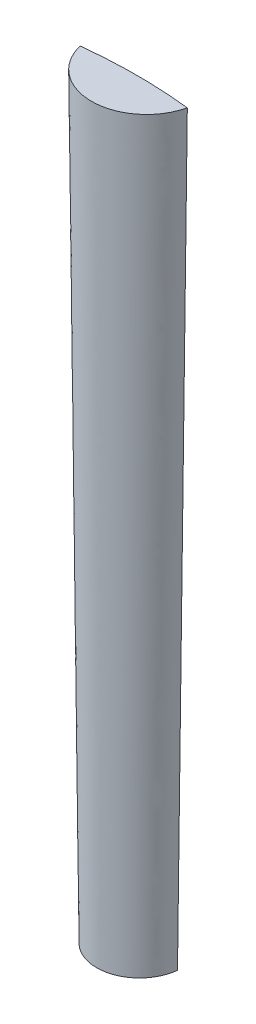
SolidWorks part; units mm, degrees
material "Maple"
ref_plane "Front Plane" through (0, 0, 0) normal (0, 0, 1) x (1, 0, 0)
ref_plane "Top Plane" through (0, 0, 0) normal (0, 1, 0) x (1, 0, 0)
ref_plane "Right Plane" through (0, 0, 0) normal (1, 0, 0) x (0, 0, -1)
sketch "Model" plane through (0, 0, 0) normal (0, 0, 1) x (1, 0, 0)
  line L0 (47.9999, 0) -> (57.149, 660.4)
  line L1 (40.86, 0) -> (46.3494, 660.4)
  line L2 (33.72, 0) -> (35.5498, 660.4)
  line L3 (26.5801, 0) -> (24.7503, 660.4)
  line L4 (19.4401, 0) -> (13.9507, 660.4)
  line L5 (12.3002, 0) -> (3.1511, 660.4)
  line L6 (51.151, 0) -> (60.3001, 660.4)
  line L7 (9.1491, 0) -> (0, 660.4)
  line L8 (51.659, 0) -> (43.9219, 0)
  line L9 (52.1725, 37.0654) -> (44.3327, 37.0654)
  line L10 (52.6572, 72.0505) -> (44.7205, 72.0505)
  line L11 (53.1147, 105.072) -> (45.0865, 105.072)
  line L12 (53.5465, 136.2402) -> (45.4319, 136.2402)
  line L13 (53.954, 165.659) -> (45.7579, 165.659)
  line L14 (54.3387, 193.4267) -> (46.0657, 193.4267)
  line L15 (54.7018, 219.6359) -> (46.3562, 219.6359)
  line L16 (55.0445, 244.3741) -> (46.6304, 244.3741)
  line L17 (55.368, 267.7238) -> (46.8891, 267.7238)
  line L18 (55.6734, 289.763) -> (47.1334, 289.763)
  line L19 (55.9616, 310.5653) -> (47.364, 310.5653)
  line L20 (56.2336, 330.2) -> (47.5816, 330.2)
  line L21 (56.4903, 348.7327) -> (47.787, 348.7327)
  line L22 (56.7327, 366.2252) -> (47.9808, 366.2252)
  line L23 (56.9614, 382.736) -> (48.1638, 382.736)
  line L24 (57.1773, 398.3201) -> (48.3365, 398.3201)
  line L25 (57.3811, 413.0295) -> (48.4996, 413.0295)
  line L26 (57.5734, 426.9133) -> (48.6534, 426.9133)
  line L27 (57.755, 440.0179) -> (48.7987, 440.0179)
  line L28 (57.9263, 452.387) -> (48.9358, 452.387)
  line L29 (58.0881, 464.0619) -> (49.0652, 464.0619)
  line L30 (58.2407, 475.0815) -> (49.1873, 475.0815)
  line L31 (58.3848, 485.4826) -> (49.3026, 485.4826)
  line L32 (58.5208, 495.3) -> (49.4114, 495.3)
  line L33 (44.9379, 0) -> (36.782, 0)
  line L34 (45.3487, 37.0654) -> (36.9874, 37.0654)
  line L35 (45.7365, 72.0505) -> (37.1813, 72.0505)
  line L36 (46.1025, 105.072) -> (37.3643, 105.072)
  line L37 (46.4479, 136.2402) -> (37.537, 136.2402)
  line L38 (46.7739, 165.659) -> (37.7, 165.659)
  line L39 (47.0817, 193.4267) -> (37.8539, 193.4267)
  line L40 (47.3722, 219.6359) -> (37.9991, 219.6359)
  line L41 (47.6464, 244.3741) -> (38.1362, 244.3741)
  line L42 (47.9051, 267.7238) -> (38.2656, 267.7238)
  line L43 (48.1494, 289.763) -> (38.3877, 289.763)
  line L44 (48.38, 310.5653) -> (38.503, 310.5653)
  line L45 (48.5976, 330.2) -> (38.6118, 330.2)
  line L46 (48.803, 348.7327) -> (38.7145, 348.7327)
  line L47 (48.9968, 366.2252) -> (38.8114, 366.2252)
  line L48 (49.1798, 382.736) -> (38.9029, 382.736)
  line L49 (49.3525, 398.3201) -> (38.9893, 398.3201)
  line L50 (49.5156, 413.0295) -> (39.0708, 413.0295)
  line L51 (49.6694, 426.9133) -> (39.1478, 426.9133)
  line L52 (49.8147, 440.0179) -> (39.2204, 440.0179)
  line L53 (49.9518, 452.387) -> (39.2889, 452.387)
  line L54 (50.0812, 464.0619) -> (39.3536, 464.0619)
  line L55 (50.2033, 475.0815) -> (39.4147, 475.0815)
  line L56 (50.3186, 485.4826) -> (39.4723, 485.4826)
  line L57 (50.4274, 495.3) -> (39.5267, 495.3)
  line L58 (37.798, 0) -> (29.6421, 0)
  line L59 (38.0034, 37.0654) -> (29.6421, 37.0654)
  line L60 (38.1973, 72.0505) -> (29.6421, 72.0505)
  line L61 (38.3803, 105.072) -> (29.6421, 105.072)
  line L62 (38.553, 136.2402) -> (29.6421, 136.2402)
  line L63 (38.716, 165.659) -> (29.6421, 165.659)
  line L64 (38.8699, 193.4267) -> (29.6421, 193.4267)
  line L65 (39.0151, 219.6359) -> (29.6421, 219.6359)
  line L66 (39.1522, 244.3741) -> (29.6421, 244.3741)
  line L67 (39.2816, 267.7238) -> (29.6421, 267.7238)
  line L68 (39.4037, 289.763) -> (29.6421, 289.763)
  line L69 (39.519, 310.5653) -> (29.6421, 310.5653)
  line L70 (39.6278, 330.2) -> (29.6421, 330.2)
  line L71 (39.7305, 348.7327) -> (29.6421, 348.7327)
  line L72 (39.8274, 366.2252) -> (29.6421, 366.2252)
  line L73 (39.9189, 382.736) -> (29.6421, 382.736)
  line L74 (40.0053, 398.3201) -> (29.6421, 398.3201)
  line L75 (40.0868, 413.0295) -> (29.6421, 413.0295)
  line L76 (40.1638, 426.9133) -> (29.6421, 426.9133)
  line L77 (40.2364, 440.0179) -> (29.6421, 440.0179)
  line L78 (40.3049, 452.387) -> (29.6421, 452.387)
  line L79 (40.3696, 464.0619) -> (29.6421, 464.0619)
  line L80 (40.4307, 475.0815) -> (29.6421, 475.0815)
  line L81 (40.4883, 485.4826) -> (29.6421, 485.4826)
  line L82 (40.5427, 495.3) -> (29.6421, 495.3)
  line L83 (30.6581, 0) -> (22.5021, 0)
  line L84 (30.6581, 37.0654) -> (22.2967, 37.0654)
  line L85 (30.6581, 72.0505) -> (22.1028, 72.0505)
  line L86 (30.6581, 105.072) -> (21.9199, 105.072)
  line L87 (30.6581, 136.2402) -> (21.7471, 136.2402)
  line L88 (30.6581, 165.659) -> (21.5841, 165.659)
  line L89 (30.6581, 193.4267) -> (21.4302, 193.4267)
  line L90 (30.6581, 219.6359) -> (21.285, 219.6359)
  line L91 (30.6581, 244.3741) -> (21.1479, 244.3741)
  line L92 (30.6581, 267.7238) -> (21.0185, 267.7238)
  line L93 (30.6581, 289.763) -> (20.8964, 289.763)
  line L94 (30.6581, 310.5653) -> (20.7811, 310.5653)
  line L95 (30.6581, 330.2) -> (20.6723, 330.2)
  line L96 (30.6581, 348.7327) -> (20.5696, 348.7327)
  line L97 (30.6581, 366.2252) -> (20.4727, 366.2252)
  line L98 (30.6581, 382.736) -> (20.3812, 382.736)
  line L99 (30.6581, 398.3201) -> (20.2948, 398.3201)
  line L100 (30.6581, 413.0295) -> (20.2133, 413.0295)
  line L101 (30.6581, 426.9133) -> (20.1364, 426.9133)
  line L102 (30.6581, 440.0179) -> (20.0637, 440.0179)
  line L103 (30.6581, 452.387) -> (19.9952, 452.387)
  line L104 (30.6581, 464.0619) -> (19.9305, 464.0619)
  line L105 (30.6581, 475.0815) -> (19.8694, 475.0815)
  line L106 (30.6581, 485.4826) -> (19.8118, 485.4826)
  line L107 (30.6581, 495.3) -> (19.7574, 495.3)
  line L108 (23.5181, 0) -> (15.3622, 0)
  line L109 (23.3127, 37.0654) -> (14.9514, 37.0654)
  line L110 (23.1188, 72.0505) -> (14.5636, 72.0505)
  line L111 (22.9359, 105.072) -> (14.1977, 105.072)
  line L112 (22.7631, 136.2402) -> (13.8522, 136.2402)
  line L113 (22.6001, 165.659) -> (13.5262, 165.659)
  line L114 (22.4462, 193.4267) -> (13.2184, 193.4267)
  line L115 (22.301, 219.6359) -> (12.9279, 219.6359)
  line L116 (22.1639, 244.3741) -> (12.6538, 244.3741)
  line L117 (22.0345, 267.7238) -> (12.395, 267.7238)
  line L118 (21.9124, 289.763) -> (12.1507, 289.763)
  line L119 (21.7971, 310.5653) -> (11.9202, 310.5653)
  line L120 (21.6883, 330.2) -> (11.7025, 330.2)
  line L121 (21.5856, 348.7327) -> (11.4971, 348.7327)
  line L122 (21.4887, 366.2252) -> (11.3033, 366.2252)
  line L123 (21.3972, 382.736) -> (11.1203, 382.736)
  line L124 (21.3108, 398.3201) -> (10.9476, 398.3201)
  line L125 (21.2293, 413.0295) -> (10.7845, 413.0295)
  line L126 (21.1524, 426.9133) -> (10.6307, 426.9133)
  line L127 (21.0797, 440.0179) -> (10.4854, 440.0179)
  line L128 (21.0112, 452.387) -> (10.3483, 452.387)
  line L129 (20.9465, 464.0619) -> (10.2189, 464.0619)
  line L130 (20.8854, 475.0815) -> (10.0968, 475.0815)
  line L131 (20.8278, 485.4826) -> (9.9815, 485.4826)
  line L132 (20.7734, 495.3) -> (9.8727, 495.3)
  line L133 (16.3782, 0) -> (8.6411, 0)
  line L134 (15.9674, 37.0654) -> (8.1276, 37.0654)
  line L135 (15.5796, 72.0505) -> (7.6429, 72.0505)
  line L136 (15.2137, 105.072) -> (7.1854, 105.072)
  line L137 (14.8682, 136.2402) -> (6.7536, 136.2402)
  line L138 (14.5422, 165.659) -> (6.3461, 165.659)
  line L139 (14.2344, 193.4267) -> (5.9614, 193.4267)
  line L140 (13.9439, 219.6359) -> (5.5983, 219.6359)
  line L141 (13.6698, 244.3741) -> (5.2556, 244.3741)
  line L142 (13.411, 267.7238) -> (4.9321, 267.7238)
  line L143 (13.1667, 289.763) -> (4.6267, 289.763)
  line L144 (12.9362, 310.5653) -> (4.3386, 310.5653)
  line L145 (12.7185, 330.2) -> (4.0665, 330.2)
  line L146 (12.5131, 348.7327) -> (3.8098, 348.7327)
  line L147 (12.3193, 366.2252) -> (3.5675, 366.2252)
  line L148 (12.1363, 382.736) -> (3.3387, 382.736)
  line L149 (11.9636, 398.3201) -> (3.1228, 398.3201)
  line L150 (11.8005, 413.0295) -> (2.919, 413.0295)
  line L151 (11.6467, 426.9133) -> (2.7267, 426.9133)
  line L152 (11.5014, 440.0179) -> (2.5451, 440.0179)
  line L153 (11.3643, 452.387) -> (2.3738, 452.387)
  line L154 (11.2349, 464.0619) -> (2.212, 464.0619)
  line L155 (11.1128, 475.0815) -> (2.0594, 475.0815)
  line L156 (10.9975, 485.4826) -> (1.9153, 485.4826)
  line L157 (10.8887, 495.3) -> (1.7793, 495.3)
  point P316 (0, 0)
ref_plane "Plane1" through (0, 37.07, 0) normal (0, 1, 0) x (1, 0, 0)
ref_plane "Plane2" through (0, 413.03, 0) normal (0, 1, 0) x (1, 0, 0)
sketch "Sketch2" plane through (0, 37.07, 0) normal (0, 1, 0) x (1, 0, 0)
  line L0 (22.5021, 0) -> (37.798, 0) construction
  line L4 (30.6581, 0) -> (22.5021, 0) construction
  line L5 (30.6581, 0) -> (22.2967, 0) construction
  line L6 (37.798, 0) -> (29.6421, 0) construction
  line L7 (30.1501, 0) -> (30.1501, -241.3) construction
  line L8 (30.1501, 0) -> (30.1501, -20) construction
  line L9 (30.1501, 0) -> (30.1501, 60) construction
  line L10 (8.7751, 0) -> (51.5251, 0) construction
  arc A0 (51.4416, -0.9412) -> (8.8585, -0.9412) centre (30.1501, -241.3) ccw
  arc A1 (8.7751, 0) -> (8.8585, -0.9412) centre (30.1501, 1.4219) ccw construction
  arc A3 (8.8585, -0.9412) -> (51.4416, -0.9412) centre (30.1501, 1.4219) ccw
  point P17 (30.1501, 0)
  point P20 (51.4076, -0.9253)
  dimension "D1" = 241.3
  dimension "D2" = 20
  dimension "D3" = 60
  dimension "D4" = 42.75
sketch "Sketch4" plane through (0, 413.03, 0) normal (0, 1, 0) x (1, 0, 0)
  line L0 (37.798, 0) -> (22.5021, 0) construction
  line L1 (37.798, 0) -> (29.6421, 0) construction
  line L2 (44.9379, 0) -> (36.782, 0) construction
  line L3 (30.6581, 0) -> (22.5021, 0) construction
  line L4 (30.6581, 0) -> (22.2967, 0) construction
  line L5 (30.1501, 0) -> (30.1501, -241.3) construction
  line L6 (30.1501, 0) -> (30.1501, -22.6) construction
  line L7 (57.2001, 0) -> (3.1001, 0) construction
  circle A0 centre (30.1501, -241.3) radius 241.3 construction
  arc A1 (57.2001, 0) -> (56.8889, -1.4861) centre (30.1501, 4.8875) cw construction
  arc A2 (3.4112, -1.4861) -> (56.8889, -1.4861) centre (30.1501, -241.3) cw
  arc A3 (3.4112, -1.4861) -> (3.1001, 0) centre (30.1501, 4.8875) cw construction
  arc A4 (56.8889, -1.4861) -> (3.4112, -1.4861) centre (30.1501, 4.8875) cw
  point P18 (30.1501, 0)
  point P21 (53.3782, 3.2801)
  point P22 (1.6999, -2.0699)
  dimension "D1" = 241.3
  dimension "D2" = 22.6
  dimension "D3" = 54.1
loft "Loft1" add profiles "Sketch4", "Sketch2" connector at (3.4112, 413.03, 1.4861) connector at (8.8585, 37.07, 0.9412)
sketch "Sketch5" plane through (0, 0, 0) normal (0, 0, 1) x (1, 0, 0)
  line L0 (51.151, 0) -> (51.151, -3.25) construction
  line L1 (51.151, -3.25) -> (9.1491, -3.25) construction
  line L2 (9.1491, -3.25) -> (9.1491, 0) construction
  line L3 (51.151, 0) -> (9.1491, 0) construction
  line L10 (47.9999, 0) -> (47.9999, -42) construction
  line L11 (40.86, 0) -> (40.86, -66) construction
  line L12 (33.72, 0) -> (33.72, -90) construction
  line L13 (26.5801, 0) -> (26.5801, -114) construction
  line L14 (19.4401, 0) -> (19.4401, -138) construction
  line L15 (12.3002, 0) -> (12.3002, -162) construction
  dimension "D1" = 3.25
  dimension "D2" = 42
  dimension "D3" = 66
  dimension "D4" = 90
  dimension "D5" = 114
  dimension "D6" = 138
  dimension "D7" = 162
sketch "Sketch7" plane through (0, 0, 0) normal (0, 0, 1) x (1, 0, 0)
  line L0 (47.9999, -42) -> (50.9999, -42) construction
  line L1 (40.86, -66) -> (43.86, -66) construction
  line L2 (33.72, -90) -> (36.72, -90) construction
  line L3 (26.5801, -114) -> (29.5801, -114) construction
  line L4 (19.4401, -138) -> (22.4401, -138) construction
  line L5 (12.3002, -162) -> (15.3002, -162) construction
  circle A0 centre (50.9999, -42) radius 5
  circle A6 centre (43.86, -66) radius 5
  circle A7 centre (36.72, -90) radius 5
  circle A8 centre (29.5801, -114) radius 5
  circle A9 centre (22.4401, -138) radius 5
  circle A10 centre (15.3002, -162) radius 5
  dimension "D7" = 10
  dimension "D8" = 10
  dimension "D9" = 10
  dimension "D10" = 10
  dimension "D11" = 10
  dimension "D12" = 10
  dimension "D1" = 3
  dimension "D2" = 3
  dimension "D3" = 3
  dimension "D4" = 3
  dimension "D5" = 3
  dimension "D6" = 3
